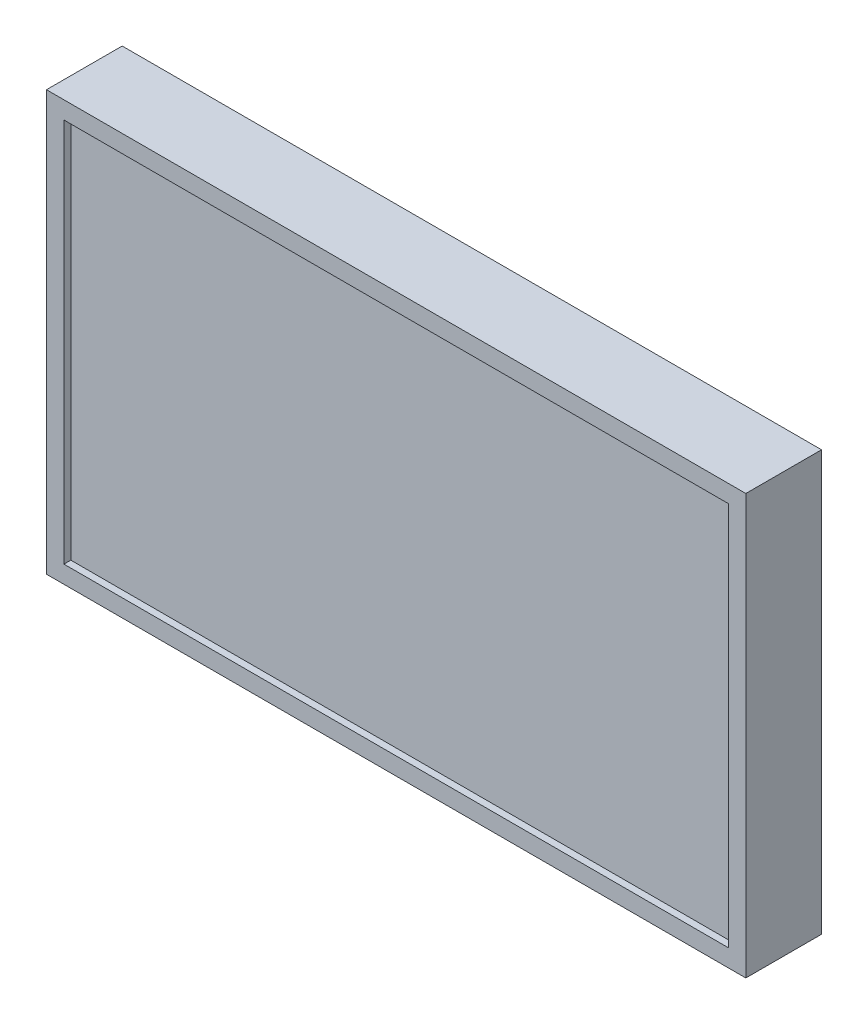
SolidWorks part; units mm, degrees
ref_plane "Front Plane" through (0, 0, 0) normal (0, 0, 1) x (1, 0, 0)
ref_plane "Top Plane" through (0, 0, 0) normal (0, 1, 0) x (1, 0, 0)
ref_plane "Right Plane" through (0, 0, 0) normal (1, 0, 0) x (0, 0, -1)
sketch "Sketch2" plane through (0, 0, 0) normal (0, 0, 1) x (1, 0, 0)
  line L1 (-254, -152.4) -> (254, -152.4)
  line L2 (-254, -152.4) -> (-254, 152.4)
  line L3 (-254, 152.4) -> (254, 152.4)
  line L4 (254, -152.4) -> (254, 152.4)
  line L5 (-254, -152.4) -> (254, 152.4) construction
  line L6 (-254, 152.4) -> (254, -152.4) construction
  point P0 (0, 0)
  dimension "D1" = 508
  dimension "D2" = 304.8
extrude "Boss-Extrude1" add sketch "Sketch2" along normal blind 55
hole_wizard "M6x1.0 Tapped Hole1" positions "Sketch3" profile "Sketch5" tap size "M6x1.0" standard "ANSI Metric"
sketch "Sketch3" plane through (0, 0, 0) normal (0, 0, -1) x (-1, 0, 0)
  line L1 (-50, -50) -> (50, -50)
  line L2 (-50, -50) -> (-50, 50)
  line L3 (-50, 50) -> (50, 50)
  line L4 (50, -50) -> (50, 50)
  line L5 (-50, -50) -> (50, 50) construction
  line L6 (-50, 50) -> (50, -50) construction
  point P2 (50, 50)
  point P35 (-50, -50)
  point P36 (-50, 50)
  point P37 (50, -50)
  dimension "D1" = 100
sketch "Sketch5" plane through (-50, 50, 0) normal (1, 0, 0) x (0, 1, 0)
  line L0 (0, 0) -> (0, 18.5022)
  line L1 (0, 18.5022) -> (2.5, 17)
  line L2 (2.5, 17) -> (2.5, 0)
  line L5 (2.5, 0) -> (0, 0)
  line L10 (0, 18.5022) -> (-2.5, 17) construction
  line L11 (0, -6.35) -> (0, 107.95) construction
  dimension "Tap Drill Dia." = 5
  dimension "Tap Drill Depth" = 17
  dimension "Drill Angle" = 118
cosmetic thread "Hole Thread1" parameters "D1"=12, "D2"=6
cosmetic thread "Hole Thread2" parameters "D1"=12, "D2"=6
cosmetic thread "Hole Thread3" parameters "D1"=12, "D2"=6
cosmetic thread "Hole Thread4" parameters "D1"=12, "D2"=6
sketch "Sketch6" plane through (0, 0, 55) normal (0, 0, 1) x (1, 0, 0)
  line L1 (-241.3, -139.7) -> (241.3, -139.7)
  line L2 (-241.3, -139.7) -> (-241.3, 139.7)
  line L3 (-241.3, 139.7) -> (241.3, 139.7)
  line L4 (241.3, -139.7) -> (241.3, 139.7)
  line L5 (-241.3, -139.7) -> (241.3, 139.7) construction
  line L6 (-241.3, 139.7) -> (241.3, -139.7) construction
  point P0 (0, 0)
  dimension "D1" = 482.6
  dimension "D2" = 279.4
extrude "Cut-Extrude1" cut sketch "Sketch6" against normal blind 5
